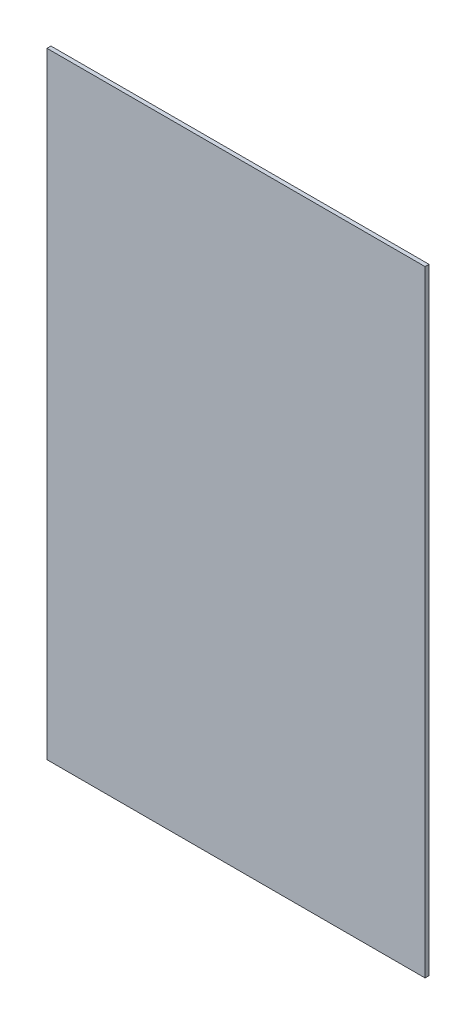
SolidWorks part; units mm, degrees
ref_plane "Plan de face" through (0, 0, 0) normal (0, 0, 1) x (1, 0, 0)
ref_plane "Plan de dessus" through (0, 0, 0) normal (0, 1, 0) x (1, 0, 0)
ref_plane "Plan de droite" through (0, 0, 0) normal (1, 0, 0) x (0, 0, -1)
sketch "Esquisse1" plane through (0, 0, 0) normal (0, 0, 1) x (1, 0, 0)
  line L1 (-67.5541, 66.6563) -> (218.4459, 66.6563)
  line L2 (-67.5541, 66.6563) -> (-67.5541, -399.3437)
  line L3 (-67.5541, -399.3437) -> (218.4459, -399.3437)
  line L4 (218.4459, 66.6563) -> (218.4459, -399.3437)
  dimension "D1" = 286
  dimension "D2" = 466
extrude "Boss.-Extru.1" add sketch "Esquisse1" along normal blind 3
equation "\"EpaisseurPlaque\"= 3"
equation "\"D1@Boss.-Extru.1\"=\"EpaisseurPlaque\""
equation "\"ProfondeurBoite\"=460"
equation "\"LongueurSyphon\"=170"
equation "\"LargeurSyphon\"=120"
equation "\"HauteurCoteDroit\"= 490"
equation "\"HauteurCoteGauche\"= 540"
equation "\"HauteurSolSyphon\"= 300"
equation "\"HauteurSyphon\"=\"HauteurCoteGauche\"-\"HauteurSolSyphon\""
equation "\"LargeurBoite\"= \"LargeurDroite\" + \"LargeurGauche\" + \"LargeurSyphon\""
equation "\"D2@Esquisse1\"=\"ProfondeurBoite\" + 2 * \"EpaisseurPlaque\""
equation "\"D1@Esquisse1\"=\"LargeurBoite\" + 2 * \"EpaisseurPlaque\""
equation "\"LargeurDroite\"=10"
equation "\"LargeurGauche\"=150"
